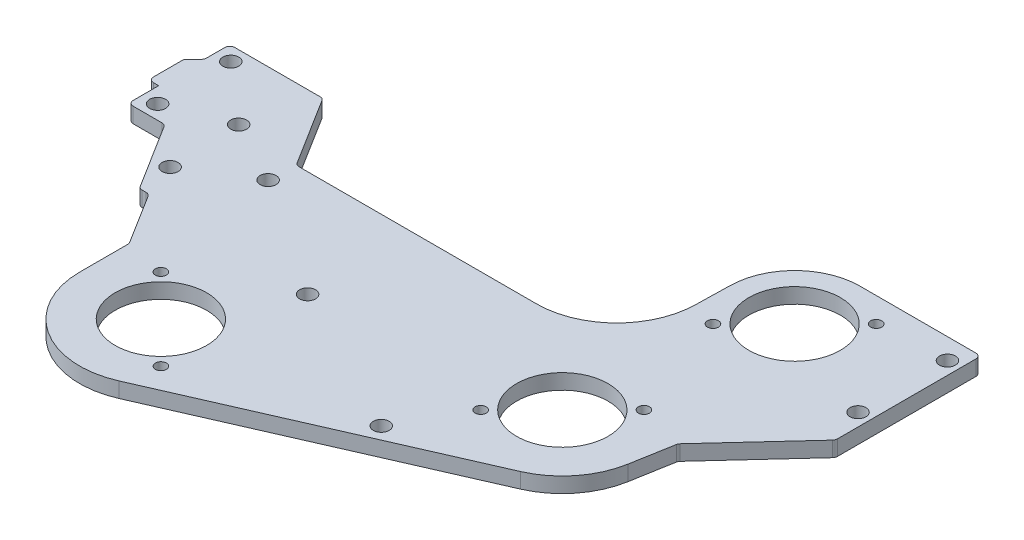
SolidWorks part; units mm, degrees
material "6061 Alloy"
ref_plane "Front Plane" through (0, 0, 0) normal (0, 0, 1) x (1, 0, 0)
ref_plane "Top Plane" through (0, 0, 0) normal (0, 1, 0) x (1, 0, 0)
ref_plane "Right Plane" through (0, 0, 0) normal (1, 0, 0) x (0, 0, -1)
sketch "Sketch1" plane through (0, 0, 0) normal (0, 1, 0) x (1, 0, 0)
  line L1 (-62.0382, -79.8833) -> (25.1671, -41.6958)
  line L5 (39.9402, -22.8907) -> (42.2751, -9.5867)
  line L6 (42.2751, -9.5867) -> (65.831, 16.0128)
  line L16 (-92.7762, 6.1643) -> (-17.7344, 6.1643)
  line L19 (65.831, 61.4936) -> (28.0466, 61.4936)
  line L20 (65.831, 16.0128) -> (65.831, 61.4936)
  line L24 (-218.6325, 207.5765) -> (-97.2237, 13.2819) construction
  line L25 (-106.6713, 28.4011) -> (-92.7762, 6.1643)
  line L26 (-72.2583, -56.6285) -> (15.031, -18.5085) construction
  line L27 (-72.2269, -82.0164) -> (109.3231, -82.0164) construction
  line L28 (15.0167, -18.5164) -> (15.0167, -82.0164) construction
  line L29 (7.3775, 31.2763) -> (7.6, 41.2639)
  line L33 (-110.9585, -24.6526) -> (-138.654, 19.6694) construction
  line L34 (-110.9585, -24.6526) -> (-126.1313, -0.371) construction
  line L36 (-135.7546, 28.4011) -> (-106.6713, 28.4011)
  line L37 (-97.6599, -56.6285) -> (-97.6599, -41.1417)
  line L38 (-107.9634, -24.6526) -> (-97.6599, -41.1417)
  line L40 (-107.9634, -24.6526) -> (-110.9585, -24.6526)
  line L42 (-138.9296, 17.2827) -> (-138.9296, 6.1643)
  line L43 (-92.7762, 6.1643) -> (-138.9296, 6.1643) construction
  line L44 (-138.9296, 6.1643) -> (-135.7546, 6.1643)
  line L45 (-135.7546, 6.1643) -> (-135.7546, -3.3607)
  line L46 (-135.7546, -3.3607) -> (-124.2632, -3.3607)
  line L47 (-124.2632, -3.3607) -> (-110.9585, -24.6526)
  line L48 (-135.7546, 6.1643) -> (-135.7546, 28.4011) construction
  line L49 (-138.9296, 17.2827) -> (-135.7546, 20.4577)
  line L50 (-135.7546, 20.4577) -> (-135.7546, 28.4011)
  circle A0 centre (28.0466, 41.0458) radius 14.29
  circle A1 centre (15.031, -18.5085) radius 14.29
  circle A2 centre (-72.2583, -56.6285) radius 14.29
  arc A4 (39.9402, -22.8907) -> (25.1671, -41.6958) centre (15.0167, -18.5164) cw
  circle A7 centre (15.031, -18.5085) radius 25.4 construction
  circle A8 centre (-72.2583, -56.6285) radius 25.4 construction
  circle A9 centre (-28.6137, -37.5685) radius 22.225 construction
  circle A10 centre (28.0466, 41.0458) radius 30.48 construction
  circle A11 centre (15.031, -18.5085) radius 30.48 construction
  arc A14 (-17.7344, 6.1643) -> (7.3775, 31.2763) centre (-17.7344, 31.2763) ccw
  arc A15 (7.6, 41.2639) -> (28.0466, 61.4936) centre (28.0466, 41.0458) cw
  arc A16 (-62.0382, -79.8833) -> (-97.6599, -56.6285) centre (-72.2583, -56.6285) cw
  point P11 (-62.0382, -79.8833)
  point P34 (15.0167, -18.5164)
  point P35 (28.0466, 41.0458)
  dimension "D2" = 50.8
  dimension "D3" = 50.8
  dimension "D4" = 44.45
  dimension "D5" = 63.5
  dimension "D7" = 60.96
  dimension "D8" = 60.96
  dimension "D1" = 140.0048
  dimension "D6" = 95.25
  dimension "D9" = 50.8
  dimension "D10" = 143.51
extrude "Boss-Extrude1" add sketch "Sketch1" along normal blind 4.7625
hole_wizard "#10 Clearance Hole1" positions "Sketch2" profile "Sketch3" hole size "#10" standard "ANSI Inch" end condition through all
sketch "Sketch2" plane through (0, 4.7625, 0) normal (0, 1, 0) x (1, 0, 0)
  point P0 (61.8305, 55.0158)
  point P3 (61.8305, 27.0758)
  point P7 (-130.9921, 23.9443)
  point P10 (-130.9921, 1.0843)
sketch "Sketch3" plane through (61.8305, 4.7625, -55.0158) normal (1, 0, 0) x (0, 0, 1)
  line L0 (0, 0) -> (0, 4.7625)
  line L1 (0, 4.7625) -> (2.4892, 4.7625)
  line L2 (2.4892, 4.7625) -> (2.4892, 0)
  line L5 (2.4892, 0) -> (0, 0)
  line L11 (0, -6.35) -> (0, 107.95) construction
  dimension "Thru Hole Dia." = 4.9784
  dimension "Thru Hole Depth" = 4.7625
sketch "Sketch4" plane through (0, 4.7625, 0) normal (0, 1, 0) x (1, 0, 0)
  line L0 (-72.2583, -56.6285) -> (-102.5432, -8.1625) construction
  line L1 (-102.5432, -8.1625) -> (-93.1193, -2.2738) construction
  line L2 (-102.5432, -8.1625) -> (-111.9672, -14.0512) construction
  line L3 (-102.5432, -8.1625) -> (-112.7324, 8.1436) construction
  line L4 (-102.5432, -8.1625) -> (-174.2713, 106.6264) construction
  line L5 (65.831, 41.0458) -> (65.831, 28.3458) construction
  dimension "D1" = 57.15
  dimension "D2" = 22.225
  dimension "D3" = 32
hole_wizard "#10 Clearance Hole2" positions "Sketch5" profile "Sketch6" hole size "#10" standard "ANSI Inch" end condition through all
sketch "Sketch5" plane through (0, 4.7625, 0) normal (0, 1, 0) x (1, 0, 0)
  point P0 (-111.9672, -14.0512)
  point P3 (-93.1193, -2.2738)
  point P7 (-112.7324, 8.1436)
sketch "Sketch6" plane through (-111.9672, 4.7625, 14.0512) normal (1, 0, 0) x (0, 0, 1)
  line L0 (0, 0) -> (0, 4.7625)
  line L1 (0, 4.7625) -> (2.4892, 4.7625)
  line L2 (2.4892, 4.7625) -> (2.4892, 0)
  line L5 (2.4892, 0) -> (0, 0)
  line L11 (0, -6.35) -> (0, 107.95) construction
  dimension "Thru Hole Dia." = 4.9784
  dimension "Thru Hole Depth" = 4.7625
sketch "Sketch7" plane through (0, 4.7625, 0) normal (0, 1, 0) x (1, 0, 0)
  line L0 (-59.5064, -69.3804) -> (-85.0103, -43.8765) construction
  line L1 (2.279, -31.2604) -> (27.783, -5.7565) construction
  line L3 (15.2946, 28.2939) -> (40.7985, 53.7978) construction
  point P7 (-72.2583, -56.6285)
  point P11 (15.031, -18.5085)
  point P13 (28.0466, 41.0458)
hole_wizard "Tap Drill for #8-32 Tap1" positions "Sketch8" profile "Sketch9" hole size "#8-32" standard "ANSI Inch" end condition through all
sketch "Sketch8" plane through (0, 4.7625, 0) normal (0, 1, 0) x (1, 0, 0)
  point P0 (-85.0103, -43.8765)
  point P3 (-59.5064, -69.3804)
  point P6 (2.279, -31.2604)
  point P9 (27.783, -5.7565)
  point P12 (15.2946, 28.2939)
  point P15 (40.7985, 53.7978)
sketch "Sketch9" plane through (-85.0103, 4.7625, 43.8765) normal (1, 0, 0) x (0, 0, 1)
  line L0 (0, 0) -> (0, 4.7625)
  line L1 (0, 4.7625) -> (1.7272, 4.7625)
  line L2 (1.7272, 4.7625) -> (1.7272, 0)
  line L5 (1.7272, 0) -> (0, 0)
  line L11 (0, -6.35) -> (0, 107.95) construction
  dimension "Thru Hole Dia." = 3.4544
  dimension "Thru Hole Depth" = 4.7625
hole_wizard "#10 Clearance Hole3" positions "Sketch11" profile "Sketch12" hole size "#10" standard "ANSI Inch" end condition through all
sketch "Sketch11" plane through (0, 4.7625, 0) normal (0, 1, 0) x (1, 0, 0)
  point P0 (-56.0414, -27.0192)
  point P3 (-8.9513, -51.0906)
sketch "Sketch12" plane through (-56.0414, 4.7625, 27.0192) normal (1, 0, 0) x (0, 0, 1)
  line L0 (0, 0) -> (0, 4.7625)
  line L1 (0, 4.7625) -> (2.4892, 4.7625)
  line L2 (2.4892, 4.7625) -> (2.4892, 0)
  line L5 (2.4892, 0) -> (0, 0)
  line L11 (0, -6.35) -> (0, 107.95) construction
  dimension "Thru Hole Dia." = 4.9784
  dimension "Thru Hole Depth" = 4.7625
fillet "Fillet1" radius 1.5875 14 edges at (-135.7546, 2.3813, 3.3607) (-124.2632, 2.3813, 3.3607) (65.831, 2.3813, -61.4936) (65.831, 2.3813, -16.0128) (42.2751, 2.3813, 9.5867) (-97.6599, 2.3813, 41.1417) (-92.7762, 2.3813, -6.1643) (-106.6713, 2.3813, -28.4011) (-138.9296, 2.3813, -17.2827) (-107.9634, 2.3813, 24.6526) (-110.9585, 2.3813, 24.6526) (-135.7546, 2.3813, -28.4011) (-135.7546, 2.3813, -20.4577) (-138.9296, 2.3813, -6.1643)
